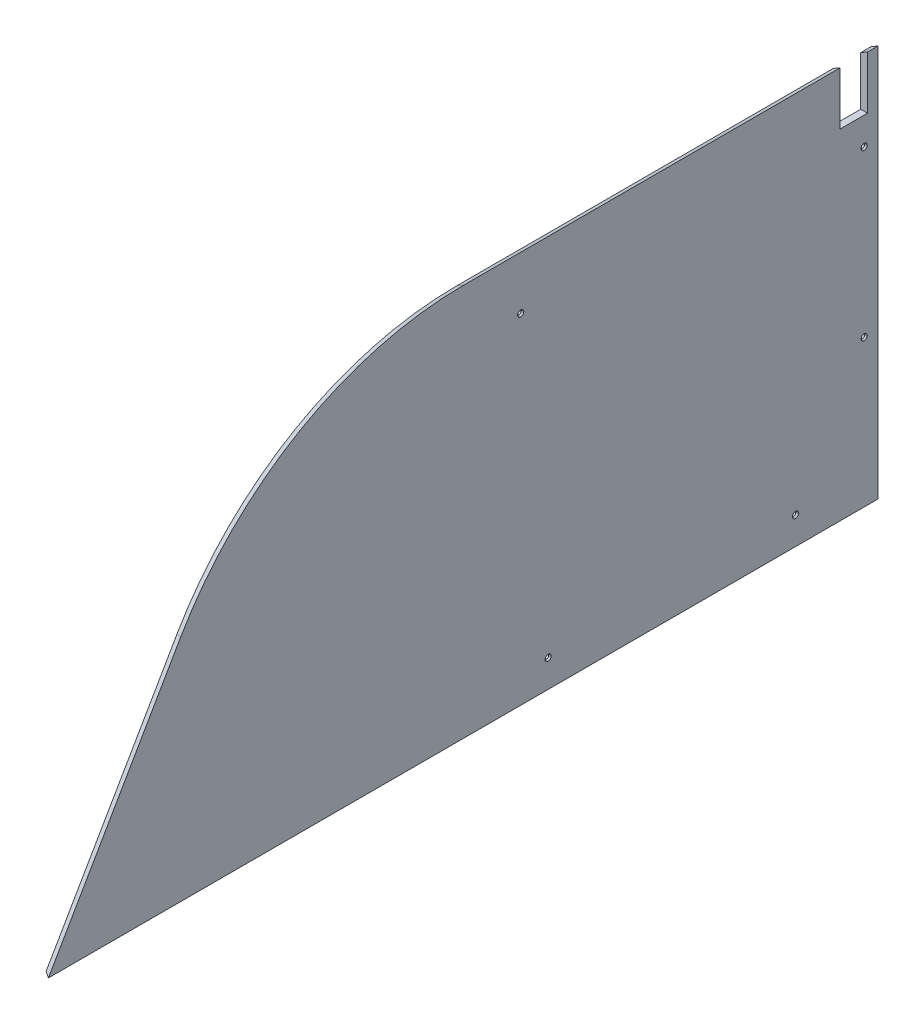
SolidWorks part; units mm, degrees
material "Delrin 2700 NC010, Low Viscosity Acetal Copolymer (SS)"
ref_plane "Front Plane" through (0, 0, 0) normal (0, 0, 1) x (1, 0, 0)
ref_plane "Top Plane" through (0, 0, 0) normal (0, 1, 0) x (1, 0, 0)
ref_plane "Right Plane" through (0, 0, 0) normal (1, 0, 0) x (0, 0, -1)
sketch "Sketch1" plane through (0, 0, 0) normal (1, 0, 0) x (0, 0, -1)
  line L0 (-123.5159, -106.1626) -> (-0.6991, 106.5624)
  line L1 (263.2655, 258.9624) -> (646.0891, 258.9624)
  line L3 (-123.5159, -106.1626) -> (646.0891, -106.1626)
  line L4 (646.0891, 258.9624) -> (646.0891, -106.1626)
  arc A0 (-0.6991, 106.5624) -> (263.2655, 258.9624) centre (263.2655, -45.8376) cw
  point P6 (87.2891, 258.9624)
  dimension "D4" = 304.8
  dimension "D1" = 60
  dimension "D2" = 365.125
  dimension "D3" = 558.8
extrude "Boss-Extrude1" add sketch "Sketch1" along normal blind 6.35
hole_wizard "CSK for #4 Flat Head Machine Screw1" positions "Sketch5" profile "Sketch4" countersink size "#4" standard "ANSI Inch" end condition through all
sketch "Sketch5" plane through (6.35, 0, 0) normal (1, 0, 0) x (0, 0, -1)
  line L1 (646.0891, -106.1626) -> (646.0891, 258.9624) construction
  line L3 (-123.5159, -106.1626) -> (646.0891, -106.1626) construction
  point P4 (633.3891, 29.7274)
  dimension "D2" = 135.89
  dimension "D3" = 12.7
sketch "Sketch4" plane through (6.35, 29.7274, -633.3891) normal (0, 1, 0) x (0, 0, -1)
  line L0 (0, 0) -> (0, 6.35)
  line L1 (0, 6.35) -> (1.6319, 6.35)
  line L2 (1.6319, 6.35) -> (1.6319, 1.4098)
  line L3 (1.6319, 1.4098) -> (2.8575, 0)
  line L5 (2.8575, 0) -> (0, 0)
  line L6 (-1.6319, 1.4098) -> (-2.8575, 0) construction
  line L11 (0, -6.35) -> (0, 107.95) construction
  dimension "Thru Hole Dia." = 3.2639
  dimension "Thru Hole Depth" = 6.35
  dimension "Near C'Sink Dia." = 5.715
  dimension "Near C'Sink Angle" = 82
hole_wizard "CSK for #4 Flat Head Machine Screw2" positions "3DSketch4" profile "Sketch7" countersink size "#4" standard "ANSI Inch" end condition through all
sketch3d "3DSketch4"
  line L0 (6.35, -106.1626, -646.0891) -> (6.35, 258.9624, -646.0891) construction
  line L2 (6.35, -106.1626, 123.5159) -> (6.35, -106.1626, -646.0891) construction
  point P0 (6.35, 207.5274, -315.8891)
  point P2 (6.35, 182.1274, -633.3891)
  dimension "D1" = 12.7
  dimension "D2" = 330.2
  dimension "D3" = 288.29
  dimension "D4" = 313.69
sketch "Sketch7" plane through (6.35, 207.5274, -315.8891) normal (0, 1, 0) x (0, 0, -1)
  line L0 (0, 0) -> (0, 6.35)
  line L1 (0, 6.35) -> (1.6319, 6.35)
  line L2 (1.6319, 6.35) -> (1.6319, 1.4098)
  line L3 (1.6319, 1.4098) -> (2.8575, 0)
  line L5 (2.8575, 0) -> (0, 0)
  line L6 (-1.6319, 1.4098) -> (-2.8575, 0) construction
  line L11 (0, -6.35) -> (0, 107.95) construction
  dimension "Thru Hole Dia." = 3.2639
  dimension "Thru Hole Depth" = 6.35
  dimension "Near C'Sink Dia." = 5.715
  dimension "Near C'Sink Angle" = 82
chamfer "Chamfer1" distance 6.096 angle 60 3 edges at (0, 0.1999, 62.1075) (0, 218.1269, -110.8655) (0, 258.9624, -454.6773) first distance on face at (0, 207.5274, -317.521)
sketch "Sketch8" plane through (6.35, 0, 0) normal (1, 0, 0) x (0, 0, -1)
  line L0 (646.0891, 256.5326) -> (263.2655, 256.5326) construction
  line L1 (636.5641, 256.5326) -> (611.1641, 256.5326)
  line L2 (636.5641, 256.5326) -> (636.5641, 207.5274)
  line L3 (636.5641, 207.5274) -> (611.1641, 207.5274)
  line L4 (611.1641, 256.5326) -> (611.1641, 207.5274)
  line L5 (646.0891, -106.1626) -> (646.0891, 256.5326) construction
  line L6 (-120.7102, -106.1626) -> (646.0891, -106.1626) construction
  dimension "D1" = 9.525
  dimension "D2" = 25.4
  dimension "D3" = 313.69
extrude "Cut-Extrude1" cut sketch "Sketch8" against normal up to next
hole_wizard "CSK for #4 Flat Head Machine Screw3" positions "3DSketch5" profile "Sketch9" countersink size "#4" standard "ANSI Inch" end condition through all
sketch3d "3DSketch5"
  line L0 (6.35, -106.1626, -646.0891) -> (6.35, 256.5326, -646.0891) construction
  line L1 (6.35, -106.1626, 120.7102) -> (6.35, -106.1626, -646.0891) construction
  point P0 (6.35, -80.7626, -569.8891)
  point P2 (6.35, -80.7626, -341.2891)
  dimension "D1" = 76.2
  dimension "D2" = 25.4
  dimension "D3" = 304.8
  dimension "D4" = 25.4
sketch "Sketch9" plane through (6.35, -80.7626, -569.8891) normal (0, 1, 0) x (0, 0, -1)
  line L0 (0, 0) -> (0, 6.35)
  line L1 (0, 6.35) -> (1.6319, 6.35)
  line L2 (1.6319, 6.35) -> (1.6319, 1.4098)
  line L3 (1.6319, 1.4098) -> (2.8575, 0)
  line L5 (2.8575, 0) -> (0, 0)
  line L6 (-1.6319, 1.4098) -> (-2.8575, 0) construction
  line L11 (0, -6.35) -> (0, 107.95) construction
  dimension "Thru Hole Dia." = 3.2639
  dimension "Thru Hole Depth" = 6.35
  dimension "Near C'Sink Dia." = 5.715
  dimension "Near C'Sink Angle" = 82
